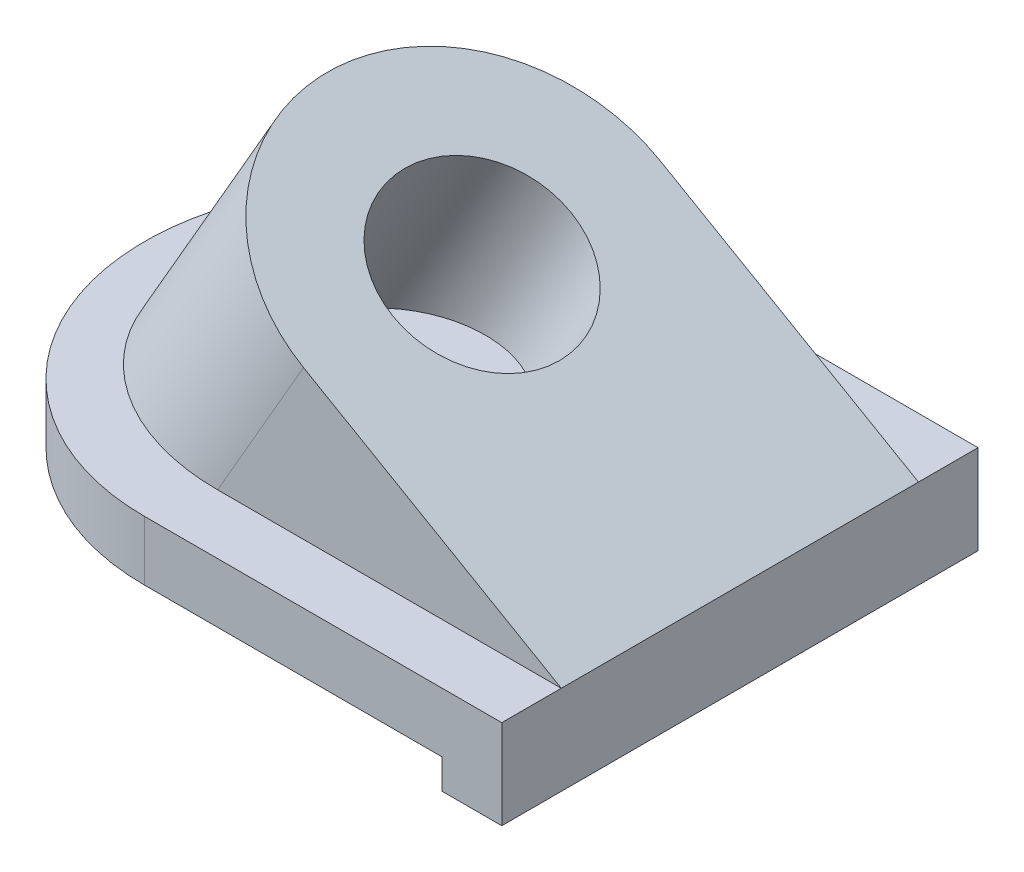
SolidWorks part; units mm, degrees
ref_plane "Front Plane" through (0, 0, 0) normal (0, 0, 1) x (1, 0, 0)
ref_plane "Top Plane" through (0, 0, 0) normal (0, 1, 0) x (1, 0, 0)
ref_plane "Right Plane" through (0, 0, 0) normal (1, 0, 0) x (0, 0, -1)
sketch "Sketch1" plane through (0, 0, 0) normal (0, 1, 0) x (1, 0, 0)
  line L3 (0, 50.8) -> (76.2, 50.8)
  line L4 (76.2, 50.8) -> (76.2, -50.8)
  line L5 (76.2, -50.8) -> (0, -50.8)
  arc A1 (0, 50.8) -> (0, -50.8) centre (0, 0) ccw
  dimension "D1" = 101.6
  dimension "D2" = 76.2
extrude "Boss-Extrude1" add sketch "Sketch1" along normal blind 12.7
sketch "Sketch2" plane through (0, 0, 50.8) normal (0, 0, 1) x (1, 0, 0)
  line L0 (76.2, 0) -> (76.2, -6.35)
  line L1 (76.2, -6.35) -> (63.5, -6.35)
  line L2 (63.5, -6.35) -> (63.5, 0)
  line L3 (0, 0) -> (76.2, 0) construction
  line L4 (63.5, 0) -> (76.2, 0)
  dimension "D1" = 6.35
  dimension "D2" = 12.7
extrude "Boss-Extrude2" add sketch "Sketch2" against normal blind 101.6
ref_axis "Axis4" through (0, 0, -49.4127) along (0, 0, 1)
ref_plane "Plane1" through (24.5493, 42.5206, 0) normal (0.5, 0.866, 0) x (0, 0, -1)
sketch "Sketch3" plane through (24.5493, 42.5206, 0) normal (0.5, 0.866, 0) x (0, 0, -1)
  line L0 (-50.8, -59.6411) -> (-38.1, -59.6411)
  line L1 (-38.1, -59.6411) -> (-38.1, 3.8589)
  line L2 (-38.1, 3.8589) -> (38.1, 3.8589)
  line L3 (-50.8, 6.35) -> (-50.8, -59.6411)
  line L4 (-50.8, -59.6411) -> (50.8, -59.6411)
  line L5 (50.8, -59.6411) -> (50.8, 6.35)
  line L6 (-50.8, 6.35) -> (-50.8, -59.6411)
  line L7 (-50.8, -59.6411) -> (50.8, -59.6411)
  line L8 (50.8, -59.6411) -> (50.8, 6.35)
  line L9 (38.1, 3.8589) -> (38.1, -59.6411)
  line L10 (38.1, -59.6411) -> (-38.1, -59.6411)
  arc A0 (38.1, 3.8589) -> (-38.1, 3.8589) centre (0, 3.8589) ccw
  circle A1 centre (0, 3.8589) radius 19.05
  ellipse E1 centre (0, 6.35) end of major axis (50.8, 6.35) minor radius 43.9941 (50.8, 6.35) -> (-50.8, 6.35) ccw
  ellipse E2 centre (0, 6.35) end of major axis (50.8, 6.35) minor radius 43.9941 (50.8, 6.35) -> (-50.8, 6.35) ccw
  dimension "D5" = 38.1
  dimension "D2" = 12.7
  dimension "D3" = 76.2
  dimension "D4" = 63.5
  dimension "D1" = 0
extrude "Boss-Extrude3" add sketch "Sketch3" against normal up to surface (36.6617 mm away) contours A1 L2 A0 | A1 L2 L1 L7 L9 region at (51.4406, 26.9949, 0) region at (-11.0504, 63.074, 0) up to face at (25.4, 12.7, 0)
